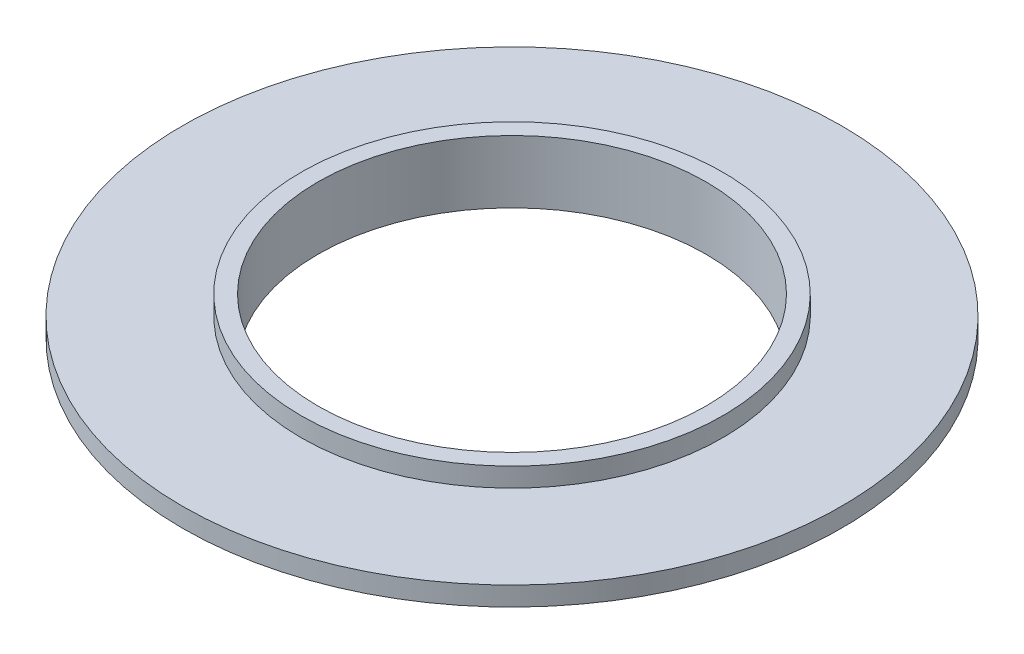
SolidWorks part; units mm, degrees
ref_plane "Alzado" through (0, 0, 0) normal (0, 0, 1) x (1, 0, 0)
ref_plane "Planta" through (0, 0, 0) normal (0, 1, 0) x (1, 0, 0)
ref_plane "Vista lateral" through (0, 0, 0) normal (1, 0, 0) x (0, 0, -1)
sketch "Croquis1" plane through (0, 0, 0) normal (0, 1, 0) x (1, 0, 0)
  circle A0 centre (0, 0) radius 26.1912
  circle A1 centre (0, 0) radius 35.5971
  dimension "D1" = 52.3824
  dimension "D2" = 71.1942
extrude "Saliente-Extruir1" add sketch "Croquis1" along normal blind 1.5
sketch "Croquis2" plane through (0, 1.5, 0) normal (0, 1, 0) x (1, 0, 0)
  circle A0 centre (0, 0) radius 60.4484
  circle A1 centre (0, 0) radius 35.5971 construction
  dimension "D1" = 120.8968
extrude "Saliente-Extruir2" add sketch "Croquis2" against normal blind 3.5
sketch "Croquis3" plane through (0, 1.5, 0) normal (0, 1, 0) x (1, 0, 0)
  circle A0 centre (0, 0) radius 35.6047
  circle A1 centre (0, 0) radius 38.6853
  circle A2 centre (0, 0) radius 60.4484 construction
  dimension "D1" = 71.2094
  dimension "D2" = 77.3706
extrude "Saliente-Extruir3" add sketch "Croquis3" along normal blind 3.5
sketch "Croquis4" plane through (0, 1.5, 0) normal (0, 1, 0) x (1, 0, 0)
  circle A0 centre (0, 0) radius 35.6047
  circle A1 centre (0, 0) radius 35.6047 construction
  dimension "D1" = 71.2094
extrude "Cortar-Extruir1" cut sketch "Croquis4" against normal through all
sketch "Croquis5" plane through (0, -2, 0) normal (0, -1, 0) x (-1, 0, 0)
  circle A0 centre (0, 0) radius 35.6047
  circle A1 centre (0, 0) radius 39.6807
extrude "Saliente-Extruir4" add sketch "Croquis5" along normal blind 4.5
sketch "Croquis6" plane through (0, 1.5, 0) normal (0, 1, 0) x (1, 0, 0)
  line L0 (0, 174.2962) -> (0, -417.5875) construction
